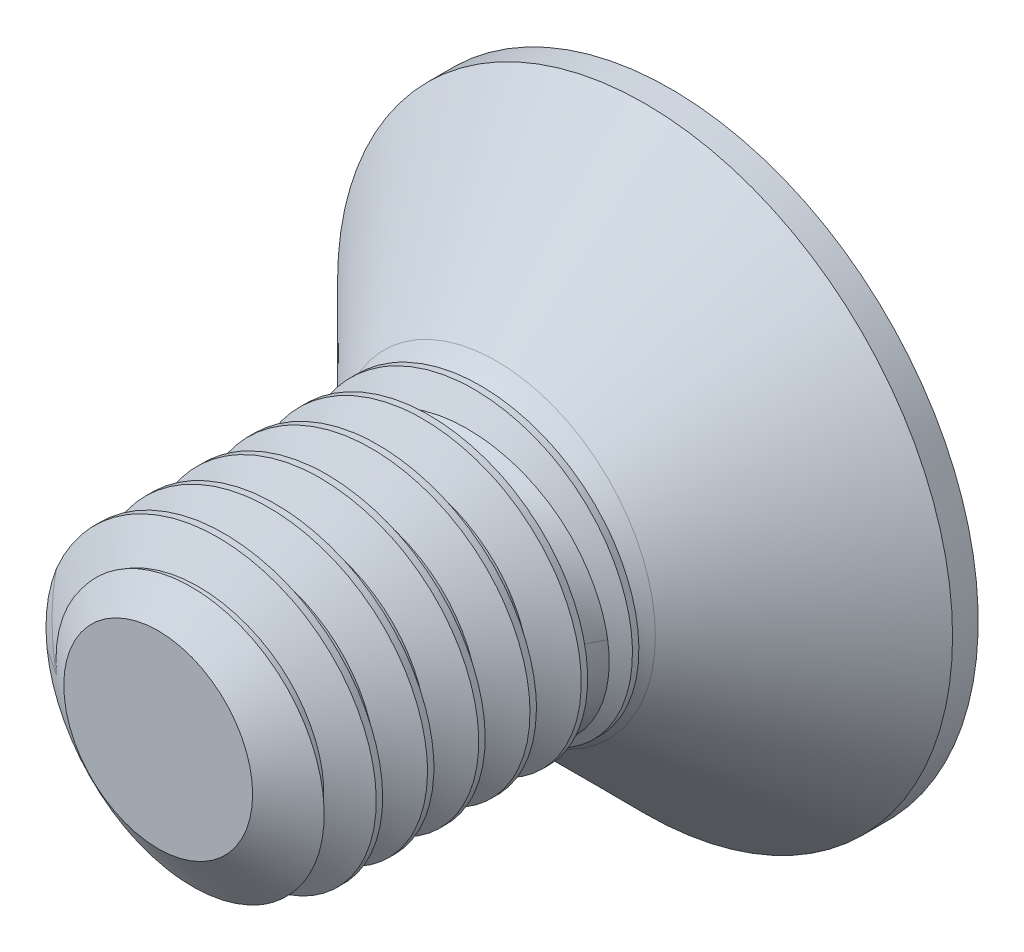
SolidWorks part; units mm, degrees
material "Alloy Steel"
ref_plane "Front Plane" through (0, 0, 0) normal (0, 0, 1) x (1, 0, 0)
ref_plane "Top Plane" through (0, 0, 0) normal (0, 1, 0) x (1, 0, 0)
ref_plane "Right Plane" through (0, 0, 0) normal (1, 0, 0) x (0, 0, -1)
sketch "Sketch1" plane through (0, 0, 0) normal (0, 0, 1) x (1, 0, 0)
  circle A0 centre (0, 0) radius 1.5
  dimension "OD" = 3
extrude "Extrude1" add sketch "Sketch1" against normal blind 5
sketch "Sketch2" plane through (0, 0, 0) normal (0, 0, 1) x (1, 0, 0)
  circle A0 centre (0, 0) radius 1.5 construction
  circle A1 centre (0, 0) radius 1.5
curve "Helix/Spiral1" pitch 0.5 height 5.5 radius 1.5 centre (0, 0, 0) axis (0, 0, -1) start towards (0, 1, 0) parameters "pitch"=0.5
sketch "Sketch3" plane through (0, 0, 0) normal (1, 0, 0) x (0, 0, -1)
  line L0 (-0.4375, 1.5) -> (-0.25, 1.1752)
  line L1 (-0.25, 1.1752) -> (-0.1875, 1.1752)
  line L2 (-0.1875, 1.1752) -> (0, 1.5)
  line L3 (-0.4375, 1.5) -> (0, 1.5)
  line L4 (-0.2188, 1.5) -> (-0.2188, 1.1752) construction
  line L5 (-0.3438, 1.3376) -> (-0.0937, 1.3376) construction
  line L6 (0, 1.5) -> (0, -1.5) construction
  dimension "D1" = 0.0625
  dimension "D2" = 0.25
  dimension "D3" = 60
sweep "Cut-Sweep1" cut profiles "Sketch3" path "Helix/Spiral1"
sketch "Sketch4" plane through (0, 0, 0) normal (1, 0, 0) x (0, 0, -1)
  line L0 (0.4053, 1.5) -> (0, 0.9212)
  line L1 (0, 0.9212) -> (0, 1.5)
  line L2 (0.4053, 1.5) -> (0, 1.5)
  line L3 (-0.4375, 1.5) -> (0, 1.5) construction
  line L4 (0, 0) -> (7.0209, 0) construction
  dimension "D1" = 55
  dimension "D2" = 0.254
revolve "Cut-Revolve1" cut sketch "Sketch4" angle 360 about L4
sketch "Sketch5" plane through (0, 0, 0) normal (1, 0, 0) x (0, 0, -1)
  line L0 (5, -1.1822) -> (5, 1.0703) construction
  line L1 (5, 1.55) -> (18.1906, 1.55)
  line L2 (5, 1.55) -> (5, 0)
  line L3 (5, 0) -> (18, 0)
  line L4 (18, 1.2198) -> (18, 0)
  line L5 (18.1906, 1.55) -> (18, 1.2198)
  line L6 (0, 0) -> (9.9695, 0) construction
  point P3 (18, 1.55)
  point P10 (18, 1.55)
  dimension "D1" = 0.3302
  dimension "Thread min" = 18
  dimension "D2" = 0.05
  dimension "D3" = 30
revolve "partially thread" [suppressed] add sketch "Sketch5" angle 360 about L6
sketch "Sketch6" plane through (0, 0, -5) normal (0, 0, -1) x (-1, 0, 0)
  circle A0 centre (0, 0) radius 3
  dimension "head dia" = 6
extrude "Extrude2" add sketch "Sketch6" against normal blind 1.7
sketch "Sketch10" plane through (0, 0, 0) normal (1, 0, 0) x (0, 0, -1)
  line L0 (4.75, -3) -> (3.3, -1.55)
  line L1 (3.3, -1.55) -> (3.3, -3)
  line L2 (4.75, -3) -> (3.3, -3)
  line L3 (0, 0) -> (3.3, 0) construction
  line L4 (3.3, 3) -> (3.3, -3) construction
  line L5 (4.75, 3) -> (3.3, 3) construction
  line L6 (3.3, 1.55) -> (3.3, 3) construction
  line L7 (4.75, 3) -> (3.3, 1.55) construction
  line L8 (3.3, 3) -> (3.3, -3) construction
  line L9 (3.3, 1.55) -> (3.3, -1.55) construction
  dimension "D1" = 45
  dimension "D2" = 0.05
revolve "Cut-Revolve2" cut sketch "Sketch10" angle 360 about L3
sketch "Sketch11" plane through (0, 0, 0) normal (1, 0, 0) x (0, 0, -1)
  line L0 (-0.25, 1.1752) -> (-0.1875, 1.1752) construction
  line L1 (4.75, 3) -> (3.3, 1.55) construction
  line L2 (2.3953, 1.1752) -> (2.3953, 0)
  line L3 (2.3953, 0) -> (3.3, 0)
  line L4 (3.3, 1.55) -> (3.3, 0)
  line L5 (0, 0) -> (3.3, 0) construction
  arc A0 (3.3, 1.55) -> (2.3953, 1.1752) centre (2.3953, 2.4547) cw
revolve "Revolve1" add sketch "Sketch11" angle 360 about L3
sketch "Sketch7" plane through (0, 0, -5) normal (0, 0, 1) x (1, 0, 0)
  line L1 (0, 1.1547) -> (-1, 0.5774)
  line L2 (-1, 0.5774) -> (-1, -0.5774)
  line L3 (-1, -0.5774) -> (0, -1.1547)
  line L4 (0, -1.1547) -> (1, -0.5774)
  line L5 (1, -0.5774) -> (1, 0.5774)
  line L6 (1, 0.5774) -> (0, 1.1547)
  circle A0 centre (0, 0) radius 1 construction
  dimension "hex dia" = 2
extrude "Cut-Extrude1" cut sketch "Sketch7" along normal blind 1.5
sketch "Sketch8" plane through (0, 0, -5) normal (0, 0, 1) x (1, 0, 0)
  circle A0 centre (0, 0) radius 1.1547
extrude "Cut-Extrude2" cut sketch "Sketch8" along normal through all draft 45
sketch "Sketch9" plane through (0, 0, 0) normal (1, 0, 0) x (0, 0, -1)
  line L0 (0, 1.5) -> (0, -1.5) construction
  line L1 (2.75, 1.5) -> (2.75, -1.5) construction
  line L2 (3.3, 1.5) -> (3.3, -1.5) construction
  line L3 (3.3, -1.55) -> (3.3, -3) construction
  dimension "D1" = 2.75
equation "\"D3@Helix/Spiral1\" = \"screw length@Extrude1\"+\"pitch@Helix/Spiral1\""
equation "\"D1@Sketch3\" = \"pitch@Helix/Spiral1\"*.125"
equation "\"D2@Sketch3\" = \"pitch@Helix/Spiral1\"*.5"
equation "\"D1@Cut-Extrude1\" = \"hex dia@Sketch7\"*.75"
equation "\"D1@Sketch9\" = \"pitch@Helix/Spiral1\"*5.5"
equation "\"D2@Sketch10\" = \"D2@Sketch5\""
